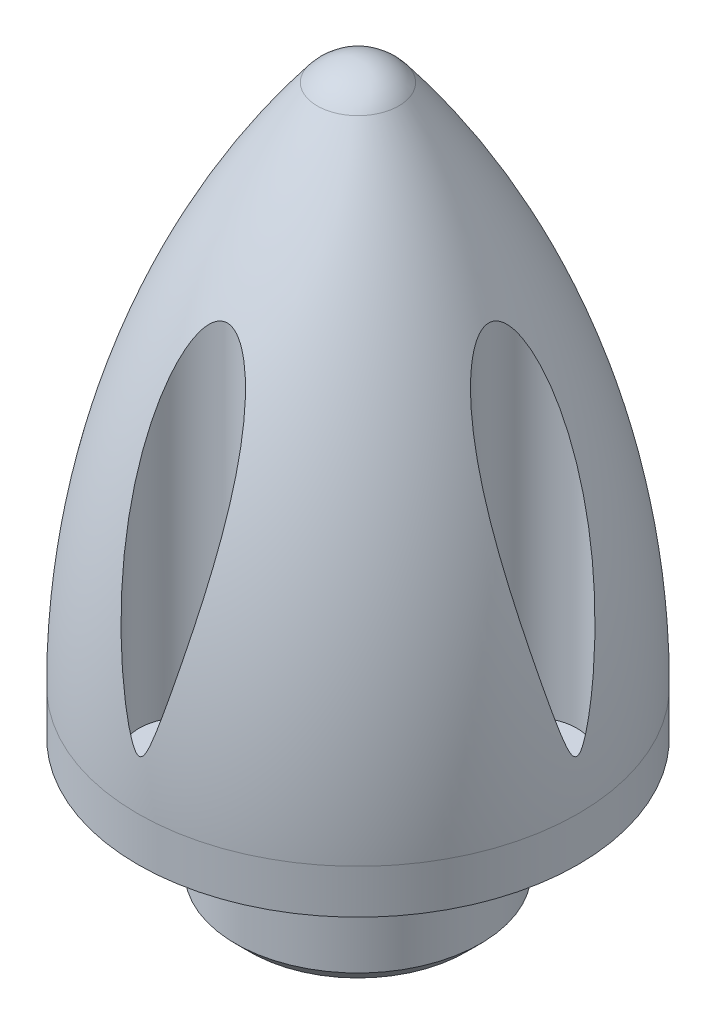
SolidWorks part; units mm, degrees
ref_plane "Front Plane" through (0, 0, 0) normal (0, 0, 1) x (1, 0, 0)
ref_plane "Top Plane" through (0, 0, 0) normal (0, 1, 0) x (1, 0, 0)
ref_plane "Right Plane" through (0, 0, 0) normal (1, 0, 0) x (0, 0, -1)
sketch "Sketch2" plane through (0, 0, 0) normal (1, 0, 0) x (0, 0, -1)
  line L0 (0, 0) -> (0, 50.8) construction
  line L1 (0, 0) -> (19.05, 0) construction
  line L2 (0, 50.8) -> (0, 47.1925)
  line L3 (19.05, 0) -> (8.89, 0)
  line L4 (19.05, 0) -> (19.05, 3.81)
  line L5 (0, 25.4) -> (15.0618, 27.7354) construction
  line L6 (0, 25.5795) -> (6.6479, 26.4308) construction
  arc A1 (0, 47.1925) -> (8.89, 0) centre (-98.5313, 4.1978) cw
  arc A2 (0, 50.8) -> (3.5286, 49.0735) centre (0, 46.331) cw
  arc A4 (19.05, 3.81) -> (3.5286, 49.0735) centre (-54.7092, 3.81) ccw
  dimension "D4" = 3.81
  dimension "D6" = 197.0626
  dimension "D1" = 50.8
  dimension "D2" = 10.16
  dimension "D3" = 3.6075
  dimension "D5" = 8.89
revolve "Revolve1" add sketch "Sketch2" angle 360 about L0
sketch "Sketch3" plane through (0, 0, 0) normal (0, -1, 0) x (1, 0, 0)
  line L0 (0, 0) -> (19.05, 0) construction
  circle A0 centre (0, 0) radius 19.05 construction
  circle A1 centre (15.1181, 0) radius 1.6205
  circle A2 centre (0, 0) radius 8.89 construction
  circle A3 centre (0, -15.1181) radius 1.6205
  circle A4 centre (-15.1181, 0) radius 1.6205
  circle A5 centre (0, 15.1181) radius 1.6205
  circle A6 centre (15.1181, 0) radius 3.81
  circle A7 centre (0, -15.1181) radius 3.81
  circle A8 centre (-15.1181, 0) radius 3.81
  circle A9 centre (0, 15.1181) radius 3.81
  point P19 (0, 0)
  point P27 (0, 0)
  dimension "D1" = 3.241
  dimension "D2" = 15.1181
  dimension "D4" = 7.62
  dimension "D3" = 4
  dimension "D5" = 4
extrude "Cut-Extrude1" cut sketch "Sketch3" against normal through all contours A3 | A4 | A1 L0 | A5 | L0 A1 | L0 A6 A1 | A6 L0 A1 | A9 A5 | A8 A4 | A7 A3 region at (15.1181, 0, 1.8223) region at (15.1181, 0, -0.6878) region at (15.1181, 0, 0.6878) region at (15.1181, 0, -1.8223) region at (0, 0, -15.1181) region at (-15.1181, 0, 0) region at (0, 0, 15.1181) region at (-3.7022, 0, -15.1181) region at (-18.8203, 0, 0) region at (-3.7022, 0, 15.1181)
ref_plane "Plane1" through (0, 6.35, 0) normal (0, -1, 0) x (-1, 0, 0)
sketch "Sketch5" plane through (0, 6.35, 0) normal (0, -1, 0) x (-1, 0, 0)
  circle A0 centre (0, 0) radius 19.05
  circle A1 centre (0, 0) radius 19.05 construction
  circle A2 centre (0, 0) radius 10.5937
  circle A3 centre (0, 0) radius 8.763
  dimension "D1" = 17.526
  dimension "D2" = 21.1874
extrude "Boss-Extrude7" add sketch "Sketch5" along normal blind 17.78 contours A2 A3 region at (10.2941, 6.35, 0)
extrude "Boss-Extrude8" add sketch "Sketch3<4>" against normal blind 6.35
sketch "Sketch3<4>" plane through (0, 0, 0) normal (0, -1, 0) x (1, 0, 0) same geometry as "Sketch3"
chamfer "Chamfer1" distance 1.27 angle 45 1 edges at (0, -11.43, -10.5937)
